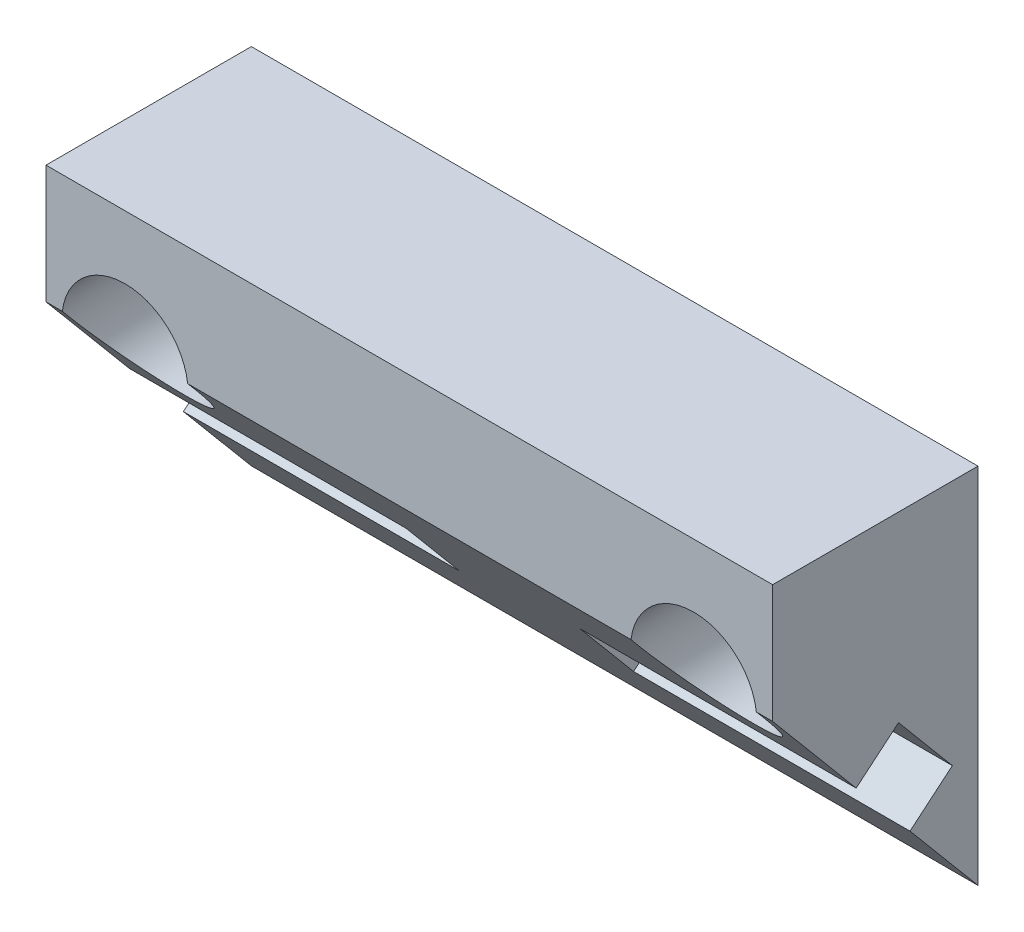
SolidWorks part; units mm, degrees
ref_plane "Front Plane" through (0, 0, 0) normal (0, 0, 1) x (1, 0, 0)
ref_plane "Top Plane" through (0, 0, 0) normal (0, 1, 0) x (1, 0, 0)
ref_plane "Right Plane" through (0, 0, 0) normal (1, 0, 0) x (0, 0, -1)
ref_plane "PL_Ym23" through (-23, 0, 0) normal (1, 0, 0) x (0, 0, -1)
sketch "SK_Body" plane through (-23, 0, 0) normal (1, 0, 0) x (0, 0, -1)
  line L0 (0, -14.9891) -> (-13, 0.5036)
  line L1 (-13, 0.5036) -> (-13, 8)
  line L2 (-13, 8) -> (0, 8)
  line L3 (0, 8) -> (0, -14.9891)
  dimension "D1" = 14.9891
  dimension "D2" = 13
  dimension "D3" = 0.5036
  dimension "D4" = 13
  dimension "D5" = 8
  dimension "D6" = 8
extrude "EX_Body" add sketch "SK_Body" along normal blind 46
sketch "SK_SkinBolts" plane through (0, 0, 0) normal (0, 0, 1) x (1, 0, 0)
  circle A0 centre (18, 0) radius 2.25
  circle A1 centre (-18, 0) radius 2.25
  dimension "D2" = 4.5
  dimension "D4" = 4.5
  dimension "D1" = 18
  dimension "D3" = 18
extrude "CUT_SkinBolts" cut sketch "SK_SkinBolts" along normal blind 13
ref_plane "PL_Xp6" through (0, 0, 6) normal (0, 0, 1) x (1, 0, 0)
sketch "SK_BoltHeads" plane through (0, 0, 6) normal (0, 0, 1) x (1, 0, 0)
  circle A0 centre (18, 0) radius 4
  circle A1 centre (-18, 0) radius 4
  dimension "D2" = 8
  dimension "D4" = 8
  dimension "D1" = 18
  dimension "D3" = 18
extrude "CUT_BoltHeads" cut sketch "SK_BoltHeads" along normal blind 7
ref_plane "PL_Yp5_5" through (5.5, 0, 0) normal (1, 0, 0) x (0, 0, -1)
sketch "SK_PlugL" plane through (5.5, 0, 0) normal (1, 0, 0) x (0, 0, -1)
  line L0 (-4.3049, -9.8588) -> (-7.7117, -5.7987)
  line L1 (-7.7117, -5.7987) -> (-5.0305, -3.549)
  line L2 (-5.0305, -3.549) -> (-1.6237, -7.609)
  line L3 (-1.6237, -7.609) -> (-4.3049, -9.8588)
  dimension "D1" = 4.3049
  dimension "D2" = 9.8588
  dimension "D3" = 7.7117
  dimension "D4" = 5.7987
  dimension "D5" = 5.0305
  dimension "D6" = 3.549
  dimension "D7" = 1.6237
  dimension "D8" = 7.609
extrude "CUT_PlugL" cut sketch "SK_PlugL" along normal blind 17.5
ref_plane "PL_Ym5_5" through (-5.5, 0, 0) normal (1, 0, 0) x (0, 0, -1)
sketch "SK_PlugR" plane through (-5.5, 0, 0) normal (1, 0, 0) x (0, 0, -1)
  line L0 (-4.3049, -9.8588) -> (-7.7117, -5.7987)
  line L1 (-7.7117, -5.7987) -> (-5.0305, -3.549)
  line L2 (-5.0305, -3.549) -> (-1.6237, -7.609)
  line L3 (-1.6237, -7.609) -> (-4.3049, -9.8588)
  dimension "D1" = 4.3049
  dimension "D2" = 9.8588
  dimension "D3" = 7.7117
  dimension "D4" = 5.7987
  dimension "D5" = 5.0305
  dimension "D6" = 3.549
  dimension "D7" = 1.6237
  dimension "D8" = 7.609
extrude "CUT_PlugR" cut sketch "SK_PlugR" against normal blind 17.5
ref_axis "AX_X" through (0, 0, -0.65) along (0, 0, 1)
ref_axis "AX_Y" through (25.3, 0, 0) along (-1, 0, 0)
ref_axis "AX_Z" through (0, 9.1495, 0) along (0, -1, 0)
sketch "SK_F_IF_Sensor" plane through (0, 0, 0) normal (1, 0, 0) x (0, 0, -1)
  line L0 (-0.3196, -14.6082) -> (-11.697, -1.0493) construction
  point P3 (-6.0083, -7.8288)
  dimension "D1" = 0.3196
  dimension "D2" = 14.6082
  dimension "D3" = 11.697
  dimension "D4" = 1.0493
